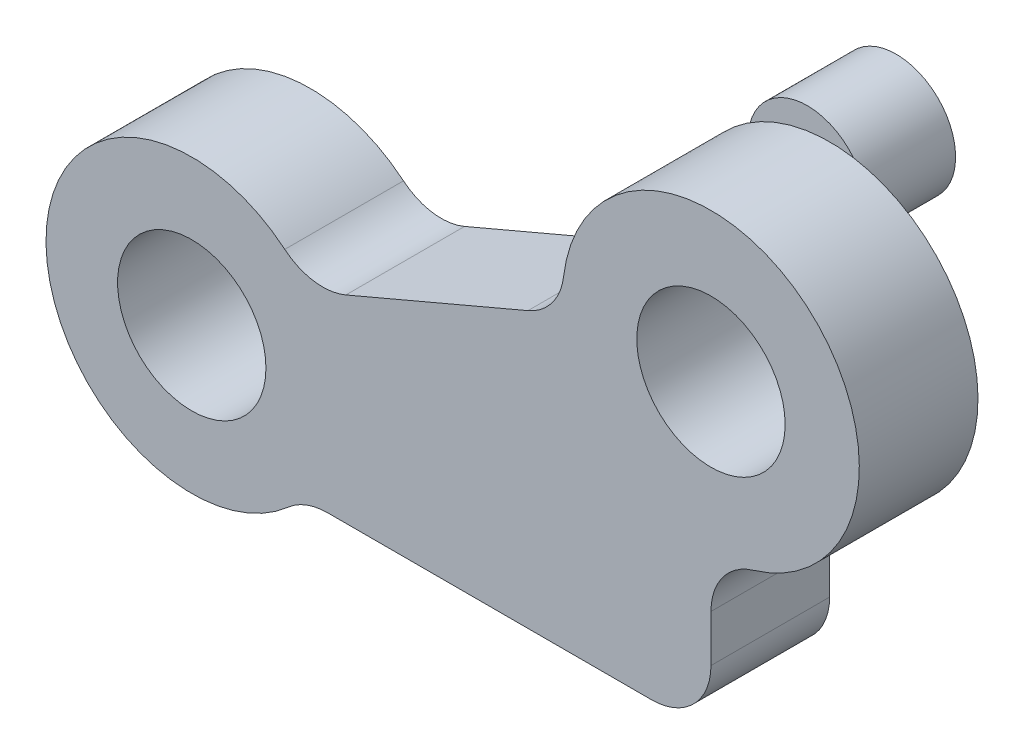
SolidWorks part; units mm, degrees
ref_plane "Front Plane" through (0, 0, 0) normal (0, 0, 1) x (1, 0, 0)
ref_plane "Top Plane" through (0, 0, 0) normal (0, 1, 0) x (1, 0, 0)
ref_plane "Right Plane" through (0, 0, 0) normal (1, 0, 0) x (0, 0, -1)
sketch "Sketch1" plane through (0, 0, 0) normal (0, 0, 1) x (1, 0, 0)
  line L0 (143.3333, 493) -> (716.6667, 493) construction
  line L1 (56.8391, 28.5799) -> (56.8391, 23.2923)
  line L2 (56.8391, 23.2923) -> (43.0826, 23.2923)
  line L3 (51.8645, 33.076) -> (43.2731, 29.4209)
  circle A2 centre (39.3406, 26.4759) radius 2.5
  circle A3 centre (56.8391, 33.5799) radius 2.5
  arc A4 (56.8391, 28.5799) -> (51.8645, 33.076) centre (56.8391, 33.5799) ccw
  arc A5 (43.2731, 29.4209) -> (43.0826, 23.2923) centre (39.3406, 26.4759) ccw
extrude "Boss-Extrude1" add sketch "Sketch1" along normal blind 4
fillet "Fillet1" radius 2 5 edges at (43.0826, 23.2923, 2) (56.8391, 23.2923, 2) (56.8391, 28.5799, 2) (43.2731, 29.4209, 2) (51.8645, 33.076, 2)
sketch "Sketch2" plane through (0, 0, 4) normal (0, 0, 1) x (1, 0, 0)
  circle A0 centre (46.1838, 27.3596) radius 1
extrude "Boss-Extrude2" add sketch "Sketch2" against normal blind 10 from offset 3.9 offset against normal yes
sketch "Sketch3" plane through (0, 0, -9.9) normal (0, 0, -1) x (-1, 0, 0)
  circle A0 centre (-46.1838, 27.3596) radius 2
extrude "Boss-Extrude3" add sketch "Sketch3" along normal blind 3
equation "\"D1@Fillet1\"=2"
